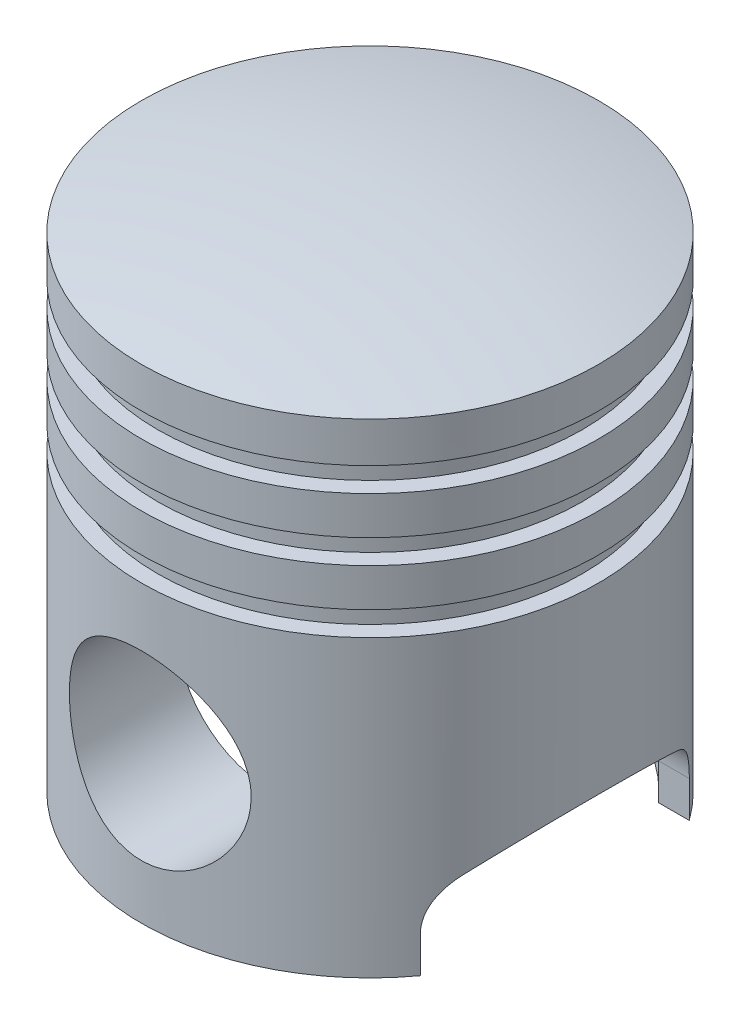
SolidWorks part; units mm, degrees
material "1345 Alloy"
ref_plane "Front Plane" through (0, 0, 0) normal (0, 0, 1) x (1, 0, 0)
ref_plane "Top Plane" through (0, 0, 0) normal (0, 1, 0) x (1, 0, 0)
ref_plane "Right Plane" through (0, 0, 0) normal (1, 0, 0) x (0, 0, -1)
sketch "Sketch1" plane through (0, 0, 0) normal (0, 1, 0) x (1, 0, 0)
  circle A0 centre (0, 0) radius 42.5
  dimension "D1" = 85
extrude "Boss-Extrude1" add sketch "Sketch1" along normal blind 90 contours A0
sketch "Sketch2" plane through (0, 90, 0) normal (0, 1, 0) x (1, 0, 0)
  circle A0 centre (0, 0) radius 39.5
  dimension "D1" = 79
extrude "Cut-Extrude5" cut sketch "Sketch2" against normal blind 4.5 from offset 7.5 flip side to cut offset against normal yes
pattern_linear "LPattern1" count 3 spacing 11.6 along (0, -1, 0) of "Cut-Extrude5"
sketch "Sketch3" plane through (0, 0, 0) normal (0, -1, 0) x (1, 0, 0)
  circle A0 centre (0, 0) radius 38
  dimension "D1" = 76
extrude "Cut-Extrude6" cut sketch "Sketch3" against normal blind 85 contours A0
dome "Dome1" faces to dome 1 distance 5 reverse direction no elliptical dome no face at (0, 90, 42.5) parameters "D1"=5
sketch "Sketch4" plane through (0, 0, 0) normal (0, 0, 1) x (1, 0, 0)
  circle A0 centre (0, 27) radius 16.9
  point P2 (0, 0)
  dimension "D1" = 33.8
  dimension "D3" = 42.5
  dimension "D2" = 27
extrude "Cut-Extrude7" cut sketch "Sketch4" against normal mid plane 85
sketch "Sketch5" plane through (0, 0, 0) normal (1, 0, 0) x (0, 0, -1)
  line L0 (25, 0) -> (-25, 0)
  line L1 (-42.5, 0) -> (42.5, 0) construction
  line L2 (25, 0) -> (25, 12)
  line L3 (-25, 0) -> (-25, 12)
  arc A0 (-25, 12) -> (25, 12) centre (0, -19.225) cw
  point P6 (0, 0)
  dimension "D4" = 40
  dimension "D1" = 50
  dimension "D2" = 12
  dimension "D3" = 12
extrude "Cut-Extrude8" cut sketch "Sketch5" against normal mid plane 85
fillet "Fillet2" radius 10 4 edges at (-31.4937, 12, -25) (-31.4937, 12, 25) (31.4937, 12, -25) (31.4937, 12, 25)
sketch "Sketch6" plane through (0, 0, 0) normal (0, 0, 1) x (1, 0, 0)
  circle A0 centre (0, 27) radius 22.5
  circle A1 centre (0, 27) radius 16.9
  dimension "D1" = 45
  dimension "D2" = 33.8
extrude "Boss-Extrude2" add sketch "Sketch6" along normal up to next from offset 19
mirror "Mirror1" about plane through (0, 0, 0) normal (0, 0, 1) of "Boss-Extrude2"
